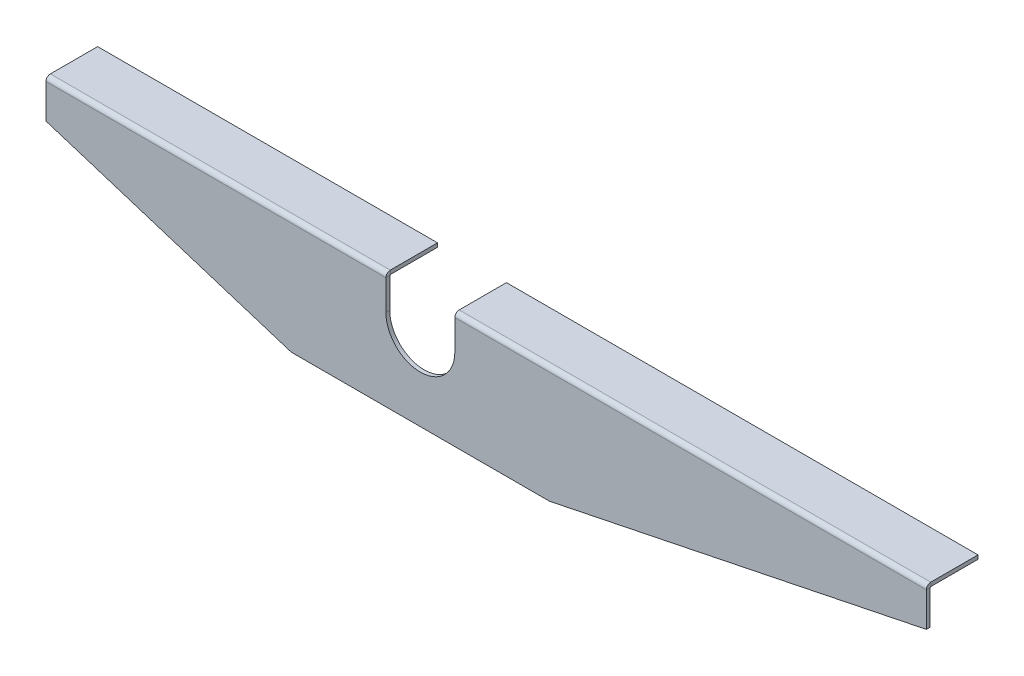
SolidWorks part; units mm, degrees
note: The reader was unsure of these and kept them because the rebuilt part matched: flange length of "Edge-Flange1".
material "ASTM A36 Steel"
ref_plane "Front Plane" through (0, 0, 0) normal (0, 0, 1) x (1, 0, 0)
ref_plane "Top Plane" through (0, 0, 0) normal (0, 1, 0) x (1, 0, 0)
ref_plane "Right Plane" through (0, 0, 0) normal (1, 0, 0) x (0, 0, -1)
sketch "Sketch1" plane through (0, 0, 0) normal (0, 0, 1) x (1, 0, 0)
  line L0 (13.35, 0) -> (13.35, 13.35)
  line L1 (13.35, 13.35) -> (196, 13.35)
  line L2 (196, 13.35) -> (196, -1.65)
  line L3 (196, -1.65) -> (50, -31.65)
  line L4 (50, -31.65) -> (-50, -31.65)
  line L5 (-50, -31.65) -> (-145, -1.65)
  line L6 (-145, -1.65) -> (-145, 13.35)
  line L7 (-145, 13.35) -> (-13.35, 13.35)
  line L8 (-13.35, 13.35) -> (-13.35, 0)
  arc A0 (-13.35, 0) -> (13.35, 0) centre (0, 0) ccw
  point P1 (0, -31.65)
  dimension "D1" = 26.7
  dimension "D2" = 100
  dimension "D3" = 0
  dimension "D4" = 15
  dimension "D5" = 15
  dimension "D6" = 145
  dimension "D7" = 196
  dimension "D8" = 45
base flange "Base-Flange1" sketch "Sketch1" thickness 1.5 reverse thickness direction no parameters "D1"=0.2
edge flange "Edge-Flange1" sketch "Sketch10" flange profiles "Sketch10", "Sketch11" flange angle 90 flange length 20 flange position material inside bend radius 0.2 thickness 1.5 relief rectangular parameters "D6"=10, "D8"=1
sketch "Sketch10" plane through (0, 13.35, -1.5) normal (0, -1, 0) x (-1, 0, 0)
  line L2 (13.35, 0) -> (13.35, 18.5)
  line L3 (13.35, 18.5) -> (145, 18.5)
  line L4 (145, 18.5) -> (145, 0)
  line L5 (145, 0) -> (13.35, 0) construction
  line L6 (145, 0) -> (13.35, 0)
sketch "Sketch11" plane through (0, 13.35, -1.5) normal (0, -1, 0) x (-1, 0, 0)
  line L2 (-196, 0) -> (-196, 18.5)
  line L3 (-196, 18.5) -> (-13.35, 18.5)
  line L4 (-13.35, 18.5) -> (-13.35, 0)
  line L5 (-13.35, 0) -> (-196, 0) construction
  line L6 (-13.35, 0) -> (-196, 0)
bend "EdgeBend1" bend radius 0.2 bend angle 90 parameters "D5"=1
bend "EdgeBend2" bend radius 0.2 bend angle 90 parameters "D5"=2
sketch "Bend-Lines1" [suppressed] plane through (0, 0, 0) normal (0, 1, 0) x (1, 0, 0)
sketch "Bounding-Box1" [suppressed] plane through (0, 0, 0) normal (0, 1, 0) x (1, 0, 0)
sheet metal parameters "Sheet-Metal1" thickness 1.5 parameters "D1"=0.2
flat pattern "Flat-Pattern1" [suppressed]
sketch "Bend-Lines2" plane through (0, 0, 0) normal (0, 1, 0) x (1, 0, 0)
sketch3d "Bounding-Box2" [suppressed]
  line L0 (350, -31.65, 0) -> (-350, -31.65, 0) construction
  line L1 (350, 13.35, 0) -> (-350, 13.35, 0) construction
  line L2 (350, -31.65, 0) -> (350, 13.35, 0) construction
  line L3 (-350, -31.65, 0) -> (-350, 13.35, 0) construction
sheet metal parameters "Sheet-Metal2" thickness 1.5 parameters "D1"=0.2
flat pattern "Flat-Pattern1"
sketch "Bend-Lines2" plane through (0, 0, 0) normal (0, 0, 1) x (1, 0, 0)
  line L0 (196, 12.3961) -> (13.35, 12.3961) construction
  line L1 (-13.35, 12.3961) -> (-145, 12.3961) construction
  line L2 (196, 12.3961) -> (13.35, 12.3961) construction
  line L3 (-13.35, 12.3961) -> (-145, 12.3961) construction
sketch3d "Bounding-Box2" [suppressed]
  line L0 (-145, -31.65, 0) -> (196, -31.65, 0) construction
  line L1 (-145, 31.4423, 0) -> (196, 31.4423, 0) construction
  line L2 (-145, -31.65, 0) -> (-145, 31.4423, 0) construction
  line L3 (196, -31.65, 0) -> (196, 31.4423, 0) construction
bend of the flat pattern "Flatten-<EdgeBend1>1"
bend of the flat pattern "Flatten-<EdgeBend2>1"
